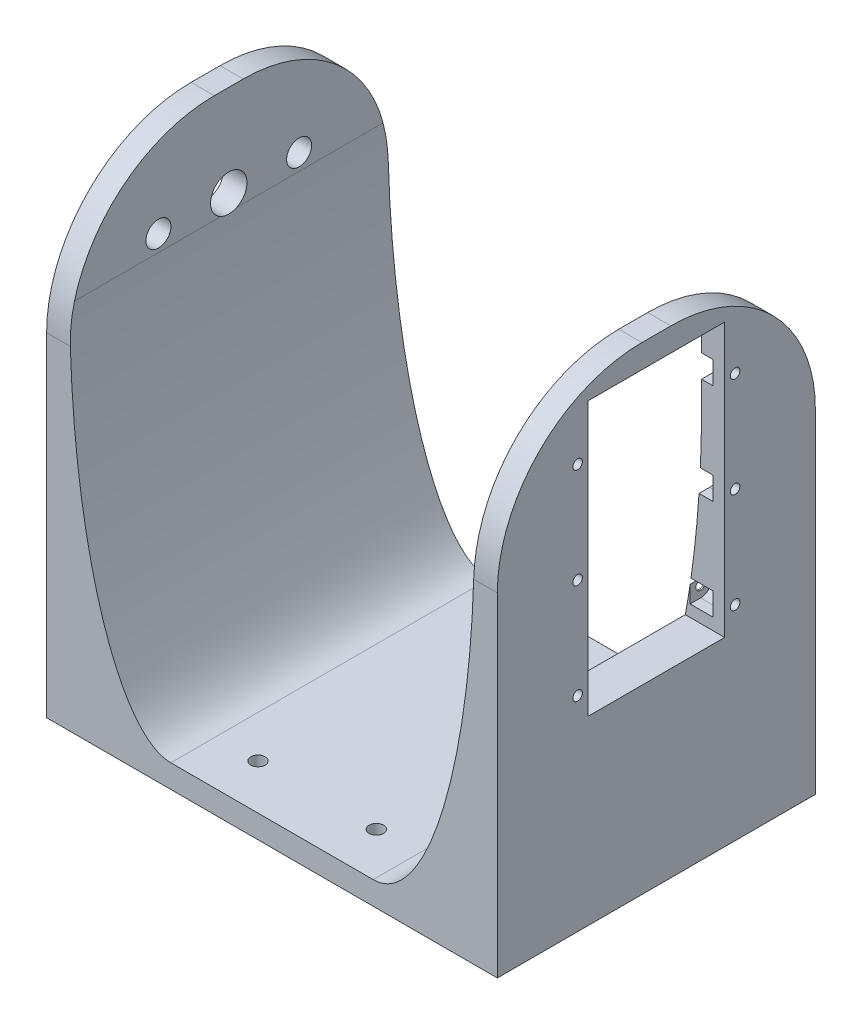
SolidWorks part; units mm, degrees
ref_plane "Front Plane" through (0, 0, 0) normal (0, 0, 1) x (1, 0, 0)
ref_plane "Top Plane" through (0, 0, 0) normal (0, 1, 0) x (1, 0, 0)
ref_plane "Right Plane" through (0, 0, 0) normal (1, 0, 0) x (0, 0, -1)
sketch "Sketch1" plane through (0, 0, 0) normal (0, 1, 0) x (1, 0, 0)
  line L1 (-49.5, -34.925) -> (49.5, -34.925)
  line L2 (-49.5, -34.925) -> (-49.5, 34.925)
  line L3 (-49.5, 34.925) -> (49.5, 34.925)
  line L4 (49.5, -34.925) -> (49.5, 34.925)
  line L5 (-49.5, -34.925) -> (49.5, 34.925) construction
  line L6 (-49.5, 34.925) -> (49.5, -34.925) construction
  point P0 (0, 0)
  dimension "D1" = 99
  dimension "D2" = 69.85
extrude "Boss-Extrude1" add sketch "Sketch1" along normal blind 105
sketch "Sketch2" plane through (0, 0, 34.925) normal (0, 0, 1) x (1, 0, 0)
  line L0 (-49.5, 105) -> (49.5, 105) construction
  line L1 (-44.42, 105) -> (44.42, 105)
  line L2 (-44.42, 105) -> (-44.42, 81.28)
  line L3 (-49.5, 105) -> (-49.5, 0) construction
  line L4 (44.42, 105) -> (44.42, 81.28)
  line L5 (0, 5.08) -> (0, 0) construction
  line L6 (-49.5, 0) -> (49.5, 0) construction
  line L7 (49.5, 105) -> (49.5, 0) construction
  line L8 (-22.225, 5.08) -> (0, 5.08) construction
  line L9 (0, 5.08) -> (22.225, 5.08) construction
  line L10 (-22.225, 81.28) -> (22.225, 81.28) construction
  line L11 (0, 5.08) -> (0, 81.28) construction
  line L12 (-22.225, 5.08) -> (22.225, 5.08)
  ellipse E0 centre (-22.225, 81.28) end of major axis (-22.225, 157.48) minor radius 22.195 (-44.42, 81.28) -> (-22.225, 5.08) ccw
  ellipse E1 centre (22.225, 81.28) end of major axis (22.225, 5.08) minor radius 22.195 (44.42, 81.28) -> (22.225, 5.08) cw
  dimension "D1" = 5.08
  dimension "D2" = 5.08
  dimension "D3" = 44.45
  dimension "D4" = 5.08
  dimension "D5" = 76.2
extrude "Cut-Extrude1" cut sketch "Sketch2" against normal through all
sketch "Sketch3" plane through (0, 0, 0) normal (0, -1, 0) x (1, 0, 0)
  line L1 (13, 25) -> (-13, 25) construction
  line L2 (13, 25) -> (13, -25) construction
  line L3 (13, -25) -> (-13, -25) construction
  line L4 (-13, 25) -> (-13, -25) construction
  line L5 (13, 25) -> (-13, -25) construction
  line L6 (13, -25) -> (-13, 25) construction
  circle A0 centre (-13, -25) radius 1.5875
  circle A1 centre (-13, 25) radius 1.5875
  circle A2 centre (13, 25) radius 1.5875
  circle A3 centre (13, -25) radius 1.5875
  point P0 (0, 0)
  dimension "D3" = 3.175
  dimension "D1" = 50
  dimension "D2" = 26
extrude "Cut-Extrude2" cut sketch "Sketch3" against normal up to next
fillet "Fillet1" radius 31.75 4 edges at (46.96, 105, 34.925) (-46.96, 105, 34.925) (-46.96, 105, -34.925) (46.96, 105, -34.925)
sketch "Sketch4" plane through (49.5, 0, 0) normal (1, 0, 0) x (0, 0, -1)
  line L0 (0, 39.82) -> (0, 44.9) construction
  line L1 (-17.3, 44.9) -> (17.3, 44.9) construction
  line L2 (-17.3, 44.9) -> (-17.3, 88.9) construction
  line L3 (-17.3, 88.9) -> (17.3, 88.9) construction
  line L4 (17.3, 44.9) -> (17.3, 88.9) construction
  line L5 (-17.3, 44.9) -> (17.3, 88.9) construction
  line L6 (-17.3, 88.9) -> (17.3, 44.9) construction
  line L7 (-15, 39.82) -> (15, 39.82)
  line L8 (-15, 39.82) -> (-15, 99.82)
  line L9 (-15, 99.82) -> (15, 99.82)
  line L10 (15, 39.82) -> (15, 99.82)
  line L13 (-3.175, 105) -> (3.175, 105) construction
  line L14 (0, 0) -> (0, 39.82) construction
  line L15 (-34.925, 0) -> (34.925, 0) construction
  circle A0 centre (-17.3, 88.9) radius 1.05
  circle A1 centre (-17.3, 66.9) radius 1.05
  circle A2 centre (-17.3, 44.9) radius 1.05
  circle A3 centre (17.3, 44.9) radius 1.05
  circle A4 centre (17.3, 66.9) radius 1.05
  circle A5 centre (17.3, 88.9) radius 1.05
  point P0 (0, 66.9)
  point P5 (0, 66.9)
  dimension "D1" = 2.1
  dimension "D2" = 44
  dimension "D3" = 34.6
  dimension "D4" = 5.08
  dimension "D5" = 38.1
  dimension "D6" = 30
  dimension "D7" = 60
extrude "Cut-Extrude3" cut sketch "Sketch4" against normal up to next
sketch "Sketch5" plane through (49.5, 0, 0) normal (1, 0, 0) x (0, 0, -1)
  line L0 (24.7067, 76.2) -> (26.035, 76.2)
  line L1 (28.575, 73.66) -> (28.575, 46.99)
  line L2 (26.035, 44.45) -> (13.335, 44.45)
  line L3 (10.795, 46.99) -> (10.795, 48.4918)
  line L4 (34.925, 73.25) -> (34.925, 0) construction
  line L5 (-34.925, 0) -> (34.925, 0) construction
  arc A0 (13.335, 44.45) -> (10.795, 46.99) centre (13.335, 46.99) cw
  arc A1 (28.575, 46.99) -> (26.035, 44.45) centre (26.035, 46.99) cw
  arc A2 (26.035, 76.2) -> (28.575, 73.66) centre (26.035, 73.66) cw
  arc A3 (22.1695, 73.5419) -> (24.7067, 76.2) centre (24.7067, 73.66) cw
  arc A4 (12.6506, 50.9379) -> (10.795, 48.4918) centre (13.335, 48.4918) ccw
  ellipse E0 centre (12.5839, 69.3669) end of major axis (14.3728, 87.9693) minor radius 9.4987 (22.1695, 73.5419) -> (12.6506, 50.9379) cw
  point P16 (10.795, 44.45)
  point P19 (28.575, 44.45)
  point P22 (28.575, 76.2)
  dimension "D7" = 2.54
  dimension "D1" = 2.54
  dimension "D3" = 12.7
  dimension "D4" = 31.75
  dimension "D5" = 6.35
  dimension "D6" = 44.45
  dimension "D9" = 1.3283
  dimension "D10" = 1.5018
extrude "Boss-Extrude2" [suppressed] add sketch "Sketch5" against normal through all
fillet "Fillet3" [suppressed] radius 2.54
sketch "Sketch6" plane through (-49.5, 0, 0) normal (-1, 0, 0) x (0, 0, 1)
  line L0 (-15.45, 84.9) -> (15.45, 84.9) construction
  line L1 (-3.175, 105) -> (3.175, 105) construction
  line L2 (0, 105) -> (0, 84.9) construction
  circle A0 centre (0, 84.9) radius 4
  circle A2 centre (-15.45, 84.9) radius 2.75
  circle A3 centre (15.45, 84.9) radius 2.75
  point P3 (0, 84.9)
  dimension "D3" = 5.5
  dimension "D4" = 8
  dimension "D1" = 20.1
  dimension "D2" = 30.9
extrude "Cut-Extrude4" cut sketch "Sketch6" against normal up to next
sketch "Sketch7" plane through (44.42, 0, 0) normal (-1, 0, 0) x (0, 0, 1)
  line L0 (-17.3, 91.4) -> (-15, 91.4)
  line L1 (-15, 99.82) -> (-15, 81.28) construction
  line L2 (-15, 91.4) -> (-15, 86.4)
  line L3 (-15, 86.4) -> (-17.3, 86.4)
  line L4 (-17.3, 69.4) -> (-15, 69.4)
  line L5 (-17.3, 64.4) -> (-15, 64.4)
  line L6 (-15, 64.4) -> (-15, 69.4)
  line L7 (-17.3, 47.4) -> (-15, 47.4)
  line L8 (-17.3, 42.4) -> (-15, 42.4)
  line L9 (-15, 42.4) -> (-15, 47.4)
  line L10 (17.3, 47.4) -> (15, 47.4)
  line L11 (17.3, 42.4) -> (15, 42.4)
  line L12 (15, 42.4) -> (15, 47.4)
  line L13 (17.3, 69.4) -> (15, 69.4)
  line L14 (15, 81.28) -> (15, 99.82) construction
  line L15 (17.3, 64.4) -> (15, 64.4)
  line L16 (15, 64.4) -> (15, 69.4)
  line L17 (17.3, 91.4) -> (15, 91.4)
  line L18 (17.3, 86.4) -> (15, 86.4)
  line L19 (15, 86.4) -> (15, 91.4)
  line L20 (-15, 39.82) -> (-15, 81.28) construction
  line L21 (15, 81.28) -> (15, 39.82) construction
  arc A0 (-17.3, 91.4) -> (-17.3, 86.4) centre (-17.3, 88.9) ccw
  arc A1 (17.3, 91.4) -> (17.3, 86.4) centre (17.3, 88.9) cw
  arc A2 (17.3, 69.4) -> (17.3, 64.4) centre (17.3, 66.9) cw
  arc A3 (17.3, 47.4) -> (17.3, 42.4) centre (17.3, 44.9) cw
  arc A4 (-17.3, 69.4) -> (-17.3, 64.4) centre (-17.3, 66.9) ccw
  arc A5 (-17.3, 47.4) -> (-17.3, 42.4) centre (-17.3, 44.9) ccw
  dimension "D1" = 2.5
extrude "Cut-Extrude5" cut sketch "Sketch7" against normal blind 2.5 and the other way blind 2.5
